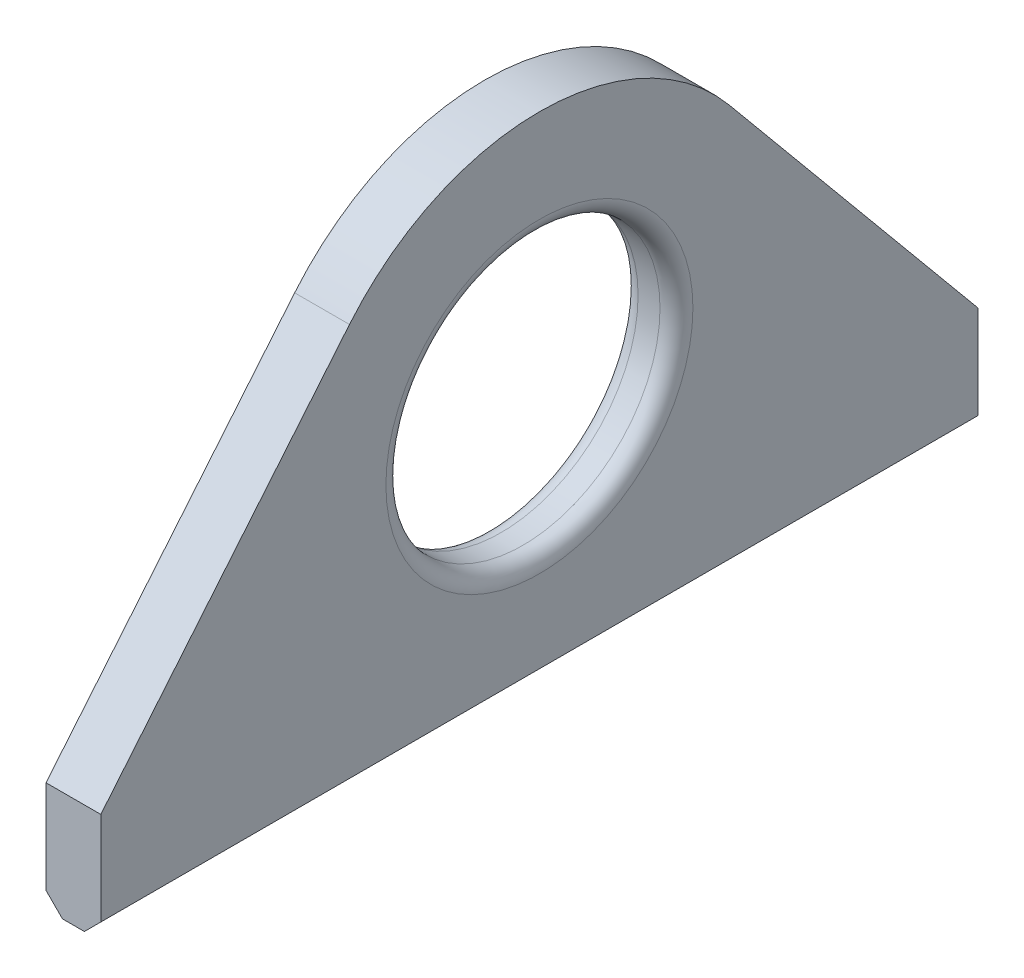
SolidWorks part; units mm, degrees
material "MS EN 10025"
ref_plane "Front Plane" through (0, 0, 0) normal (0, 0, 1) x (1, 0, 0)
ref_plane "Top Plane" through (0, 0, 0) normal (0, 1, 0) x (1, 0, 0)
ref_plane "Right Plane" through (0, 0, 0) normal (1, 0, 0) x (0, 0, -1)
sketch "Sketch1" plane through (0, 0, 0) normal (1, 0, 0) x (0, 0, -1)
  line L0 (-80, -46) -> (80, -46)
  line L1 (-80, -46) -> (-80, -26)
  line L2 (80, -46) -> (80, -26)
  line L3 (-80, -26) -> (-34.6456, 28.7173)
  line L4 (80, -26) -> (34.6456, 28.7173)
  circle A0 centre (0, 0) radius 25
  arc A1 (34.6456, 28.7173) -> (-34.6456, 28.7173) centre (0, 0) ccw
  circle A2 centre (0, 0) radius 45 construction
  point P8 (0, -46)
  dimension "D1" = 50
  dimension "D3" = 46
  dimension "D4" = 20
  dimension "D5" = 160
  dimension "D2" = 20
base flange "Base-Flange1" sketch "Sketch1" thickness 10 reverse thickness direction no parameters "D1"=3
fillet "Fillet1" radius 3 2 edges at (-10, 0, -25) (0, 0, -25)
chamfer "Chamfer1" distance 3 angle 45 2 edges at (0, -46, 0) (-10, -46, 0)
sketch "Bend-Lines1" [suppressed] plane through (0, 0, 0) normal (0, 1, 0) x (1, 0, 0)
sketch "Bounding-Box1" [suppressed] plane through (0, 0, 0) normal (0, 1, 0) x (1, 0, 0)
sheet metal parameters "Sheet-Metal2" thickness 10 parameters "D1"=3
flat pattern "Flat-Pattern2" [suppressed]
sketch "Bend-Lines2" plane through (0, 0, 0) normal (0, 1, 0) x (1, 0, 0)
sketch3d "Bounding-Box2" [suppressed]
  line L0 (-80, -46, 0) -> (80, -46, 0) construction
  line L1 (-80, 45, 0) -> (80, 45, 0) construction
  line L2 (-80, -46, 0) -> (-80, 45, 0) construction
  line L3 (80, -46, 0) -> (80, 45, 0) construction
